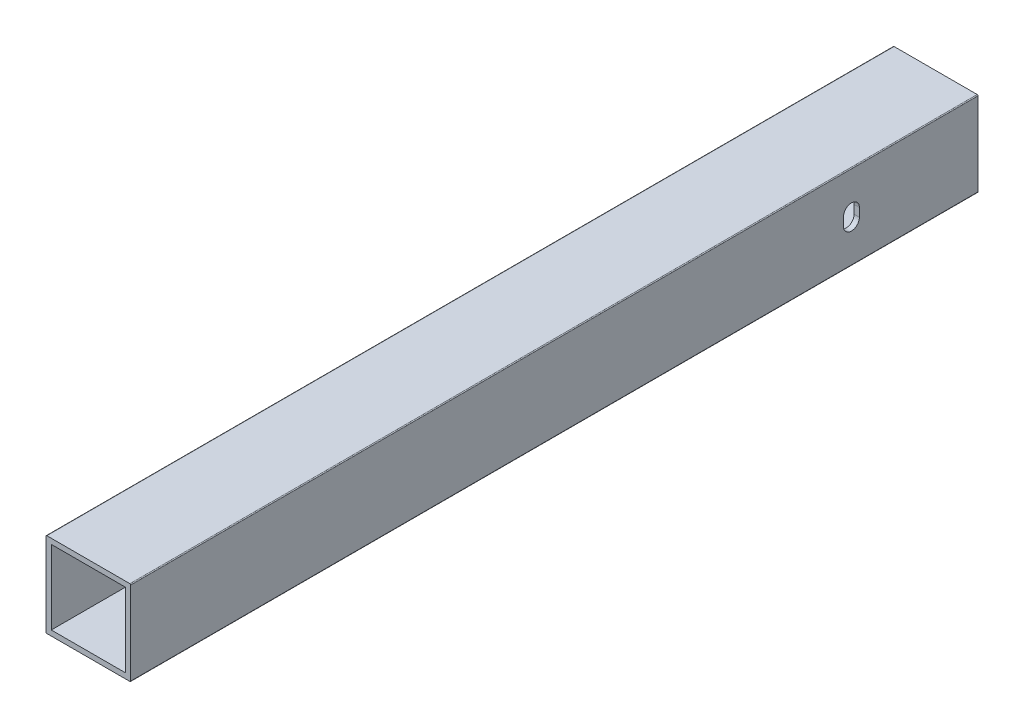
SolidWorks part; units mm, degrees
material "1060 Alloy"
ref_plane "Front Plane" through (0, 0, 0) normal (0, 0, 1) x (1, 0, 0)
ref_plane "Top Plane" through (0, 0, 0) normal (0, 1, 0) x (1, 0, 0)
ref_plane "Right Plane" through (0, 0, 0) normal (1, 0, 0) x (0, 0, -1)
ref_plane "Plane1" through (0, 0, 0) normal (0, 0, -1) x (-1, 0, 0)
sketch "Sketch1" plane through (0, 0, 0) normal (0, 0, -1) x (-1, 0, 0)
  line L4 (1.5875, -1.3335) -> (1.5875, 23.5585)
  line L5 (1.3335, 23.8125) -> (-23.5585, 23.8125)
  line L6 (-23.8125, 23.5585) -> (-23.8125, -1.3335)
  line L7 (-23.5585, -1.5875) -> (1.3335, -1.5875)
  line L9 (0, 22.225) -> (-22.225, 22.225)
  line L10 (0, 22.225) -> (0, 0)
  line L11 (0, 0) -> (-22.225, 0)
  line L12 (-22.225, 22.225) -> (-22.225, 0)
  line L13 (0, 22.225) -> (-22.225, 0) construction
  line L14 (0, 0) -> (-22.225, 22.225) construction
  arc A4 (1.3335, -1.5875) -> (1.5875, -1.3335) centre (1.3335, -1.3335) ccw
  arc A5 (1.5875, 23.5585) -> (1.3335, 23.8125) centre (1.3335, 23.5585) ccw
  arc A6 (-23.5585, 23.8125) -> (-23.8125, 23.5585) centre (-23.5585, 23.5585) ccw
  arc A7 (-23.8125, -1.3335) -> (-23.5585, -1.5875) centre (-23.5585, -1.3335) ccw
  point P24 (-11.1125, 11.1125)
  dimension "D1" = 25.4
  dimension "D2" = 25.4
  dimension "D3" = 1.5875
  dimension "D4" = 1.5875
  dimension "D5" = 1.5875
extrude "Boss-Extrude1" add sketch "Sketch1" against normal blind 254
sketch "Sketch2" plane through (-1.5875, 0, 0) normal (-1, 0, 0) x (0, 0, 1)
  line L0 (0, -1.3335) -> (0, 23.5585) construction
  line L1 (254, -1.3335) -> (0, -1.3335) construction
  line L2 (254, -1.3335) -> (254, 23.5585) construction
  circle A0 centre (12.6975, 11.3665) radius 1.5875
  circle A1 centre (241.3, 11.3665) radius 1.5875
  circle A2 centre (76.2, 11.3665) radius 6.35
  circle A3 centre (177.8, 11.3665) radius 6.35
  point P4 (0, 11.1125)
  dimension "D1" = 3.175
  dimension "D2" = 12.7
  dimension "D3" = 12.7
  dimension "D4" = 3.175
  dimension "D5" = 12.7
  dimension "D6" = 12.7
  dimension "D7" = 12.7
  dimension "D8" = 12.7
  dimension "D9" = 76.2
  dimension "D10" = 12.7
  dimension "D11" = 12.7
  dimension "D12" = 76.2
extrude "Cut-Extrude1" [suppressed] cut sketch "Sketch2" against normal through all
sketch "Sketch4" plane through (23.8125, 0, 0) normal (1, 0, 0) x (0, 0, -1)
  line L2 (-40.3145, 9.8425) -> (-40.3145, 12.3825)
  line L4 (-35.552, 9.8425) -> (-35.552, 12.3825)
  line L6 (-40.3145, 12.3825) -> (-35.552, 12.3825)
  line L7 (-40.3145, 11.1125) -> (-35.552, 11.1125)
  line L8 (0, 23.5585) -> (0, -1.3335) construction
  line L9 (0, 11.1125) -> (-49.6378, 11.1125)
  circle A0 centre (-37.9333, 9.8425) radius 2.3812
  circle A1 centre (-37.9333, 12.3825) radius 2.3812
  dimension "D1" = 4.7625
  dimension "D2" = 37.9333
  dimension "D3" = 1.27
extrude "Cut-Extrude2" cut sketch "Sketch4" against normal through all contours L6 A1 | L6 A1 A0 | L9 A0 | L9 A1 | A1 A0 | A0 L4 L7 | A1 L7 L4 | A0 L7 L2 | A1 L2 L7 | A0 region at (23.8125, 9.1445, 37.9333) region at (23.8125, 10.8001, 40.2061) region at (23.8125, 11.4249, 40.2061) region at (23.8125, 10.8001, 35.6605) region at (23.8125, 11.5673, 37.9333) region at (23.8125, 11.7352, 40.1736) region at (23.8125, 10.6577, 37.9333) region at (23.8125, 13.3931, 37.9333) region at (23.8125, 11.4249, 35.6605)
